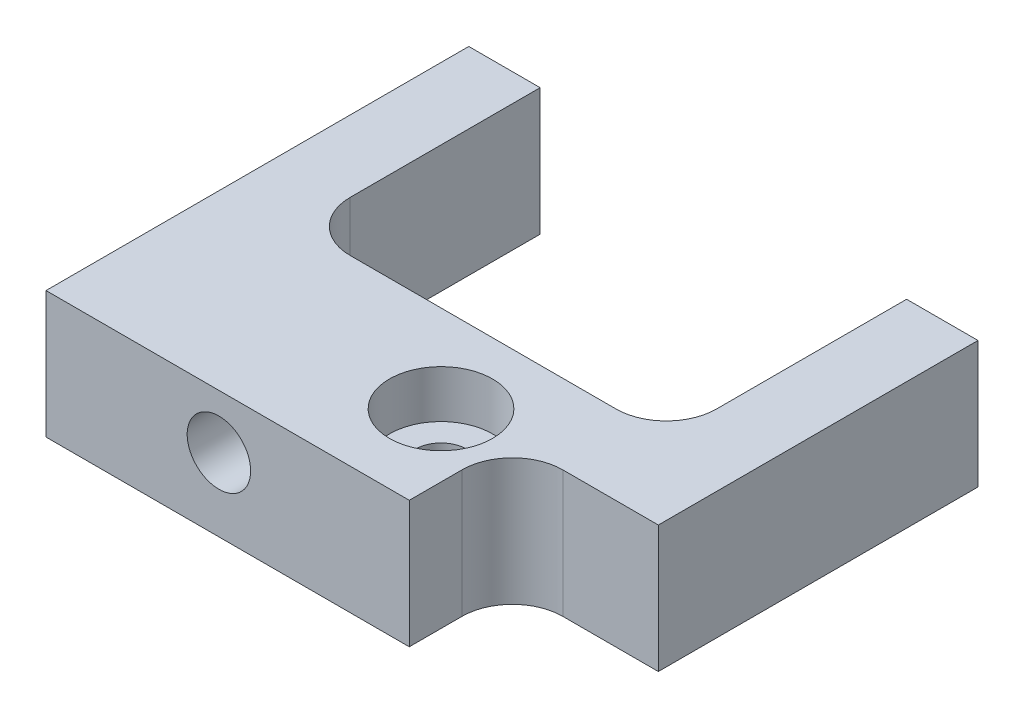
SolidWorks part; units mm, degrees
other "Markup1"
sketch "Sketch8" plane through (21.2, 4, -20.65) normal (0.586, 0.4071, -0.7006) x (0.6806, -0.7165, 0.153)
sketch "Sketch10" plane through (21.2, 4, -20.65) normal (0.586, 0.4071, -0.7006) x (0.6806, -0.7165, 0.153)
other "Markup2"
sketch "Sketch9" plane through (-10.9, 4, -20.65) normal (-0.8313, 0.2562, -0.4932) x (0.2592, 0.9637, 0.0638)
sketch "Sketch11" plane through (-10.9, 4, -20.65) normal (-0.8313, 0.2562, -0.4932) x (0.2592, 0.9637, 0.0638)
material "PTFE (general)"
ref_plane "Front" through (0, 0, 0) normal (0, 0, 1) x (1, 0, 0)
ref_plane "Top" through (0, 0, 0) normal (0, 1, 0) x (1, 0, 0)
ref_plane "Right" through (0, 0, 0) normal (1, 0, 0) x (0, 0, -1)
ref_axis "X" through (-80.9, 0, 0) along (1, 0, 0)
ref_axis "Y" through (0, -50, 0) along (0, 1, 0)
ref_axis "Z" through (0, 0, -80.9) along (0, 0, 1)
sketch "Sketch1" plane through (0, 0, 0) normal (0, 1, 0) x (1, 0, 0)
  line L0 (12, 0.5) -> (12, -6)
  line L1 (12, -6) -> (-10.9, -6)
  line L2 (-10.9, -6) -> (-10.9, 20.65)
  line L3 (-10.9, 20.65) -> (-6.4, 20.65)
  line L4 (16.7, 5.5) -> (-6.4, 5.5)
  line L5 (-6.4, 5.5) -> (-6.4, 20.65)
  line L8 (21.2, 20.65) -> (16.7, 20.65)
  line L10 (16.7, 20.65) -> (16.7, 5.5)
  line L11 (21.2, 20.65) -> (21.2, 0.5)
  line L13 (21.2, 0.5) -> (12, 0.5)
  dimension "D1" = 12
  dimension "D2" = 6
  dimension "D3" = 26.65
  dimension "D4" = 5.5
  dimension "D5" = 10.9
  dimension "D6" = 32.1
  dimension "D7" = 4.5
  dimension "D8" = 5
extrude "Boss-Extrude1" add sketch "Sketch1" along normal mid plane 8
fillet "Fillet1" radius 3.175 3 edges at (12, 0, -0.5) (16.7, 0, -5.5) (-6.4, 0, -5.5)
sketch "Sketch2" plane through (0, 0, 0) normal (0, 0, 1) x (1, 0, 0)
  line L0 (0, 0) -> (0, 0.6) construction
  circle A0 centre (0, 0.6) radius 2
  dimension "D2" = 4
  dimension "D1" = 0.6
extrude "Cut-Extrude1" cut sketch "Sketch2" against normal through all both and the other way through all
sketch "Sketch3" plane through (0, 0, 0) normal (1, 0, 0) x (0, 0, -1)
  line L0 (0, -0.6) -> (0, 0) construction
  circle A0 centre (0, -0.6) radius 2
  dimension "D2" = 4
  dimension "D1" = 0.6
extrude "Cut-Extrude2" cut sketch "Sketch3" against normal through all and the other way blind 4.5
hole_wizard "Ø1.5 (1.5) Diameter Hole1" positions "Sketch4" profile "Sketch5" hole size "Ø1.5" standard "ANSI Metric"
sketch "Sketch4" plane through (0, 0, -20.65) normal (0, 0, -1) x (-1, 0, 0)
  line L0 (-19.05, 0.6) -> (8.75, 0.6) construction
  line L3 (-19.05, 0.6) -> (-21.2, 0.6) construction
  line L4 (-21.2, 4) -> (-21.2, -4) construction
  line L7 (8.75, 0.6) -> (10.9, 0.6) construction
  line L8 (10.9, 4) -> (10.9, -4) construction
  line L10 (6.4, 4) -> (10.9, 4) construction
  point P0 (-19.05, 0.6)
  point P2 (8.75, 0.6)
  dimension "D1" = 3.4
  dimension "D2" = 27.8
sketch "Sketch5" plane through (19.05, 0.6, -20.65) normal (1, 0, 0) x (0, 1, 0)
  line L0 (0, 0) -> (0, 7.4506)
  line L1 (0, 7.4506) -> (0.75, 7)
  line L2 (0.75, 7) -> (0.75, 0)
  line L5 (0.75, 0) -> (0, 0)
  line L10 (0, 7.4506) -> (-0.75, 7) construction
  line L11 (0, -6.35) -> (0, 107.95) construction
  dimension "Hole Dia." = 1.5
  dimension "Hole Depth" = 7
  dimension "Drill Angle" = 118
hole_wizard "CBORE for M3 SHCS1" positions "Sketch6" profile "Sketch7" counterbore size "M3" standard "ANSI Metric" end condition up to next
sketch "Sketch6" plane through (0, 4, 0) normal (0, 1, 0) x (1, 0, 0)
  line L0 (0, 0) -> (8, 0) construction
  point P0 (8, 0)
  dimension "D1" = 8
sketch "Sketch7" plane through (8, 4, 0) normal (1, 0, 0) x (0, 0, 1)
  line L0 (0, 0) -> (0, 8)
  line L1 (0, 8) -> (1.6, 8)
  line L3 (1.6, 8) -> (1.6, 3)
  line L4 (1.6, 3) -> (3.25, 3)
  line L5 (3.25, 3) -> (3.25, 0)
  line L7 (3.25, 0) -> (0, 0)
  line L11 (0, -6.35) -> (0, 107.95) construction
  dimension "Thru Hole Dia." = 3.2
  dimension "Thru Hole Depth" = 8
  dimension "C'Bore Dia." = 6.5
  dimension "C'Bore Depth" = 3
